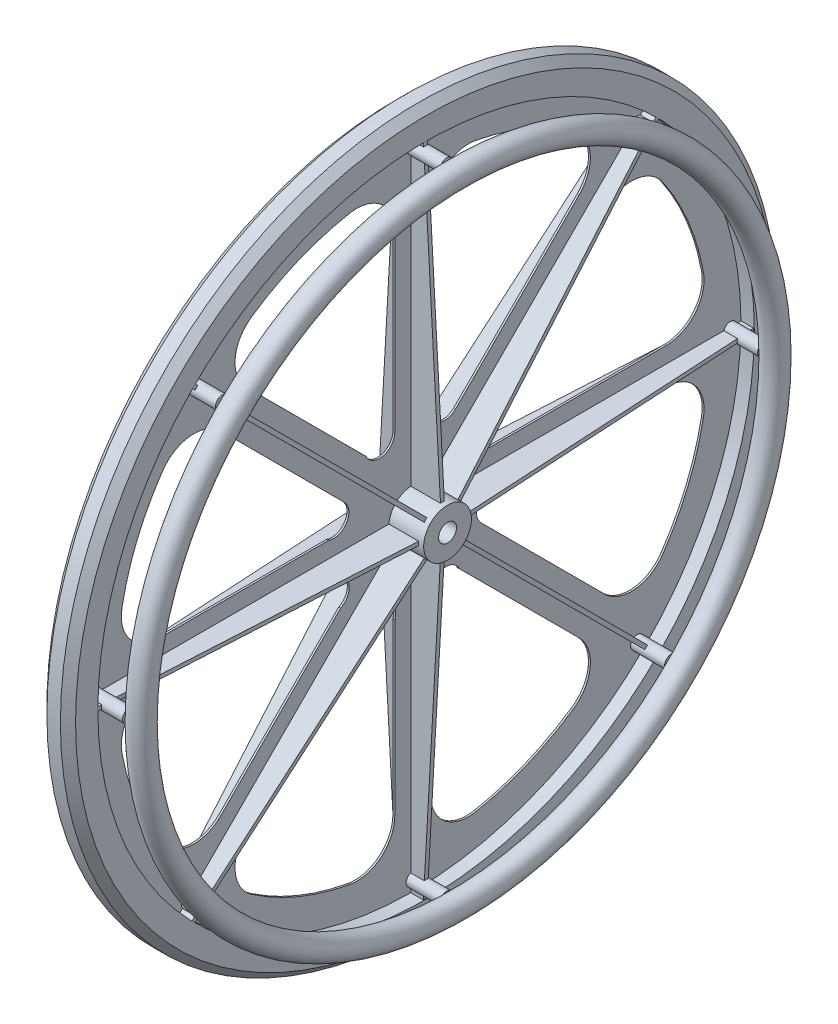
SolidWorks part; units mm, degrees
ref_plane "Plano frontal" through (0, 0, 0) normal (0, 0, 1) x (1, 0, 0)
ref_plane "Plano superior" through (0, 0, 0) normal (0, 1, 0) x (1, 0, 0)
ref_plane "Plano direito" through (0, 0, 0) normal (1, 0, 0) x (0, 0, -1)
sketch "Esboço1" plane through (0, 0, 0) normal (1, 0, 0) x (0, 0, -1)
  circle A0 centre (0, 0) radius 20
extrude "Ressalto-extrusão1" add sketch "Esboço1" along normal blind 30 and the other way blind 30
sketch "Esboço4" plane through (0, 0, 0) normal (1, 0, 0) x (0, 0, -1)
  circle A0 centre (0, 0) radius 300
  dimension "D1" = 600
extrude "Ressalto-extrusão3" add sketch "Esboço4" along normal blind 0.8 and the other way blind 0.8
sketch "Esboço10" plane through (0, 0, 0) normal (1, 0, 0) x (0, 0, -1)
  circle A0 centre (0, 0) radius 300 construction
  circle A1 centre (0, 0) radius 300
  circle A4 centre (0, 0) radius 275
  circle A5 centre (0, 0) radius 275
  dimension "D1" = 25
extrude "Ressalto-extrusão5" add sketch "Esboço10" along normal blind 12 and the other way blind 12
sketch "Esboço13" plane through (-0.8, 0, 0) normal (-1, 0, 0) x (0, 0, 1)
  line L0 (0, 0) -> (0, 249.2) construction
  line L1 (0, 0) -> (176.211, 176.211) construction
  line L2 (15, 212.3651) -> (15, 65.8652)
  line L3 (39.1429, 60.3561) -> (139.5582, 160.7714)
  circle A0 centre (0, 0) radius 300 construction
  circle A1 centre (0, 0) radius 300 construction
  arc A3 (15, 65.8652) -> (39.1429, 60.3561) centre (27.7, 65.8652) ccw
  arc A4 (139.5582, 160.7714) -> (134.2065, 209.9744) centre (117.1076, 183.2221) ccw
  arc A5 (15, 212.3651) -> (53.576, 243.3727) centre (46.75, 212.3651) cw
  arc A6 (53.576, 243.3727) -> (134.2065, 209.9744) centre (14.3293, 34.5941) cw
  dimension "D3" = 15
  dimension "D5" = 12.7
  dimension "D6" = 31.75
  dimension "D7" = 31.75
  dimension "D1" = 45
  dimension "D4" = 15
extrude "Corte-extrusão1" cut sketch "Esboço13" against normal through all contours A6 A4 L3 A3 L2 A5
ref_plane "Plano1" through (0, 280, 0) normal (0, 1, 0) x (1, 0, 0)
sketch "Esboço14" plane through (0, 0, 0) normal (0, 1, 0) x (1, 0, 0)
  line L0 (30, -20) -> (30, 20) construction
  line L1 (-26.8, -1.6) -> (26.8, -1.6)
  line L2 (-26.8, -1.6) -> (-26.8, 1.6)
  line L3 (-26.8, 1.6) -> (26.8, 1.6)
  line L4 (26.8, -1.6) -> (26.8, 1.6)
  line L5 (-26.8, -1.6) -> (26.8, 1.6) construction
  line L6 (-26.8, 1.6) -> (26.8, -1.6) construction
  point P0 (0, 0)
  dimension "D1" = 3.2
  dimension "D2" = 3.2
sketch "Esboço16" plane through (0, 280, 0) normal (0, 1, 0) x (1, 0, 0)
  line L1 (-11.115, -1.6) -> (11.115, -1.6)
  line L2 (-11.115, -1.6) -> (-11.115, 1.6)
  line L3 (-11.115, 1.6) -> (11.115, 1.6)
  line L4 (11.115, -1.6) -> (11.115, 1.6)
  line L5 (-11.115, -1.6) -> (11.115, 1.6) construction
  line L6 (-11.115, 1.6) -> (11.115, -1.6) construction
  point P0 (0, 0)
  dimension "D1" = 22.23
  dimension "D2" = 3.2
loft "Loft1" add profiles "Esboço14", "Esboço16" connector at (-26.8, 0, 1.6) connector at (-11.115, 280, 1.6)
sketch "Esboço17" plane through (0.8, 0, 0) normal (1, 0, 0) x (0, 0, -1)
  line L0 (0, 274.147) -> (0, 0) construction
  circle A0 centre (0, 266) radius 5.55
  dimension "D1" = 266
extrude "Ressalto-extrusão6" add sketch "Esboço17" along normal blind 28.5
pattern_circular "PadrãoCircular2" count 8 over 360 about axis through (12, 0, 0) along (1, 0, 0) of "Ressalto-extrusão6", "Loft1", "Corte-extrusão1"
sketch "Esboço19" plane through (30, 0, 0) normal (1, 0, 0) x (0, 0, -1)
  circle A0 centre (0, 0) radius 7.5
extrude "Corte-extrusão2" cut sketch "Esboço19" against normal through all
sketch "Esboço20" plane through (0, 0, 0) normal (0, 0, 1) x (1, 0, 0)
  line L0 (38.825, 265.523) -> (-6.8102, 265.523) construction
  line L2 (29.3, 271.4644) -> (29.3, 265.523) construction
  line L3 (29.3, 260.45) -> (29.3, 271.55) construction
  circle A0 centre (38.825, 265.523) radius 9.525
ref_axis "Eixo1" through (-33.9175, 0, 0) along (1, 0, 0)
revolve "Revolução1" add sketch "Esboço20" angle 360 about axis through (-33.9175, 0, 0) along (1, 0, 0)
chamfer "Chanfro1" distance 6.35 angle 45 2 edges at (-12, 0, -300) (12, 0, -300)
